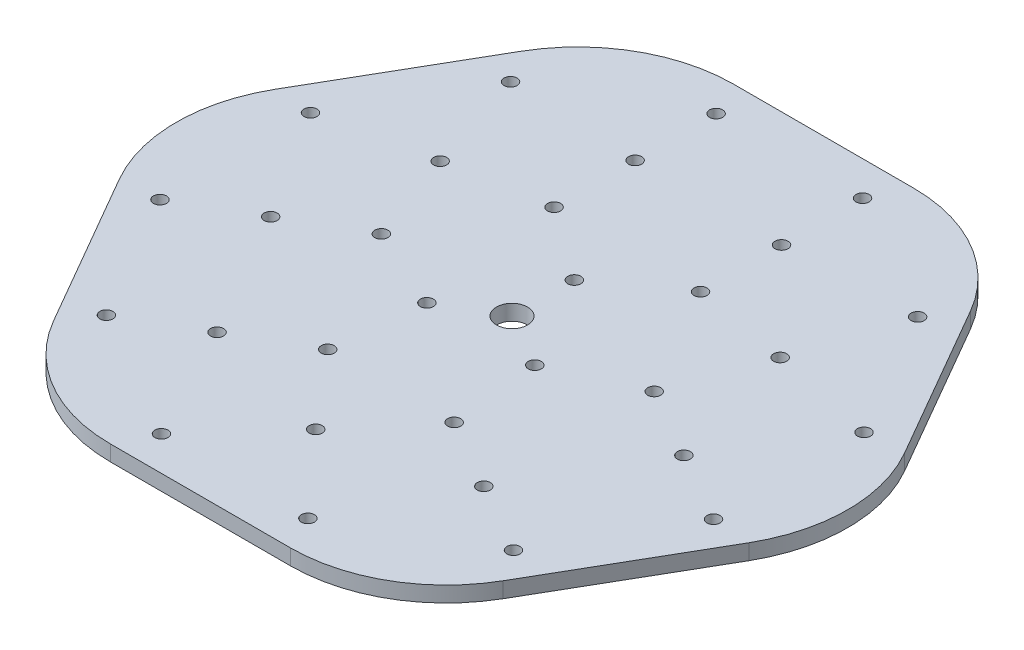
SolidWorks part; units mm, degrees
ref_plane "前视基准面" through (0, 0, 0) normal (0, 0, 1) x (1, 0, 0)
ref_plane "上视基准面" through (0, 0, 0) normal (0, 1, 0) x (1, 0, 0)
ref_plane "右视基准面" through (0, 0, 0) normal (1, 0, 0) x (0, 0, -1)
ref_axis "基准轴2" through (0, -75.8067, 0) along (0, 1, 0)
sketch "草图1" plane through (0, 0, 0) normal (0, 1, 0) x (1, 0, 0)
  line L1 (57.735, 100) -> (-57.735, 100)
  line L2 (-57.735, 100) -> (-115.4701, 0)
  line L3 (-115.4701, 0) -> (-57.735, -100)
  line L4 (-57.735, -100) -> (57.735, -100)
  line L5 (57.735, -100) -> (115.4701, 0)
  line L6 (115.4701, 0) -> (57.735, 100)
  circle A1 centre (0, 0) radius 100 construction
  dimension "D1" = 200
extrude "凸台-拉伸1" add sketch "草图1" along normal blind 5
sketch "草图2" plane through (0, 5, 0) normal (0, 1, 0) x (1, 0, 0)
  line L0 (23.5, 63) -> (23.5, 37) construction
  circle A1 centre (-23.5, 37) radius 2.1
  circle A3 centre (23.5, 37) radius 2.1
  circle A5 centre (-23.5, 63) radius 2.1
  circle A7 centre (23.5, 63) radius 2.1
  circle A16 centre (-23.5, 89) radius 2.1
  circle A17 centre (23.5, 89) radius 2.1
  circle A26 centre (23.5, 115) radius 2.1 [skipped]
  circle A27 centre (-23.5, 115) radius 2.1 [skipped]
  point P0 (23.5, 50)
  dimension "D2" = 26
  dimension "D3" = 4.2
  dimension "D4" = 4.2
  dimension "D5" = 47
  dimension "D6" = 26
  dimension "D7" = 23.5
  dimension "D8" = 47
  dimension "D9" = 50
  dimension "D10" = 2
  dimension "D11" = 0
  dimension "D12" = 4.2
  dimension "D13" = 4.2
  dimension "D14" = 26
extrude "切除-拉伸1" cut sketch "草图2" against normal through all contours A5 | A1 | A3 | A7 | A17 | A16 region at (-23.5, 5, -37) region at (23.5, 5, -37) region at (-23.5, 5, -63) region at (23.5, 5, -63)
pattern_circular "阵列(圆周)1" count 3 every 120 about axis through (0, -75.8067, 0) along (0, 1, 0) of "切除-拉伸1"
sketch "草图3" plane through (0, 5, 0) normal (0, 1, 0) x (1, 0, 0)
  line L0 (115.4701, 0) -> (57.735, 100) construction
  line L1 (86.6025, 50) -> (0, 0) construction
  circle A0 centre (65.3263, 64.8516) radius 2.1
  circle A1 centre (88.8263, 24.1484) radius 2.1
  circle A2 centre (54.5596, 31.5) radius 2.1
  dimension "D1" = 4.2
  dimension "D2" = 4.2
  dimension "D3" = 4.2
  dimension "D4" = 11
  dimension "D5" = 11
  dimension "D6" = 47
  dimension "D7" = 23.5
  dimension "D9" = 37
  dimension "D8" = 0
extrude "切除-拉伸2" cut sketch "草图3" against normal through all
pattern_circular "阵列(圆周)2" count 3 every 120 about axis through (0, -75.8067, 0) along (0, 1, 0) of "切除-拉伸2"
sketch "草图4" plane through (0, 5, 0) normal (0, 1, 0) x (1, 0, 0)
  circle A0 centre (0, 0) radius 20 construction
  circle A1 centre (0, 20) radius 2.1
  dimension "D1" = 40
  dimension "D2" = 4.2
extrude "切除-拉伸3" cut sketch "草图4" against normal through all
pattern_circular "阵列(圆周)3" count 3 over 360 about axis through (0, -75.8067, 0) along (0, 1, 0) of "切除-拉伸3"
fillet "圆角1" radius 50 6 edges at (57.735, 2.5, -100) (-57.735, 2.5, -100) (-115.4701, 2.5, 0) (-57.735, 2.5, 100) (57.735, 2.5, 100) (115.4701, 2.5, 0)
sketch "草图5" plane through (0, 5, 0) normal (0, 1, 0) x (1, 0, 0)
  circle A0 centre (0, 0) radius 5
  dimension "D1" = 10
extrude "切除-拉伸4" cut sketch "草图5" against normal through all and the other way through all
